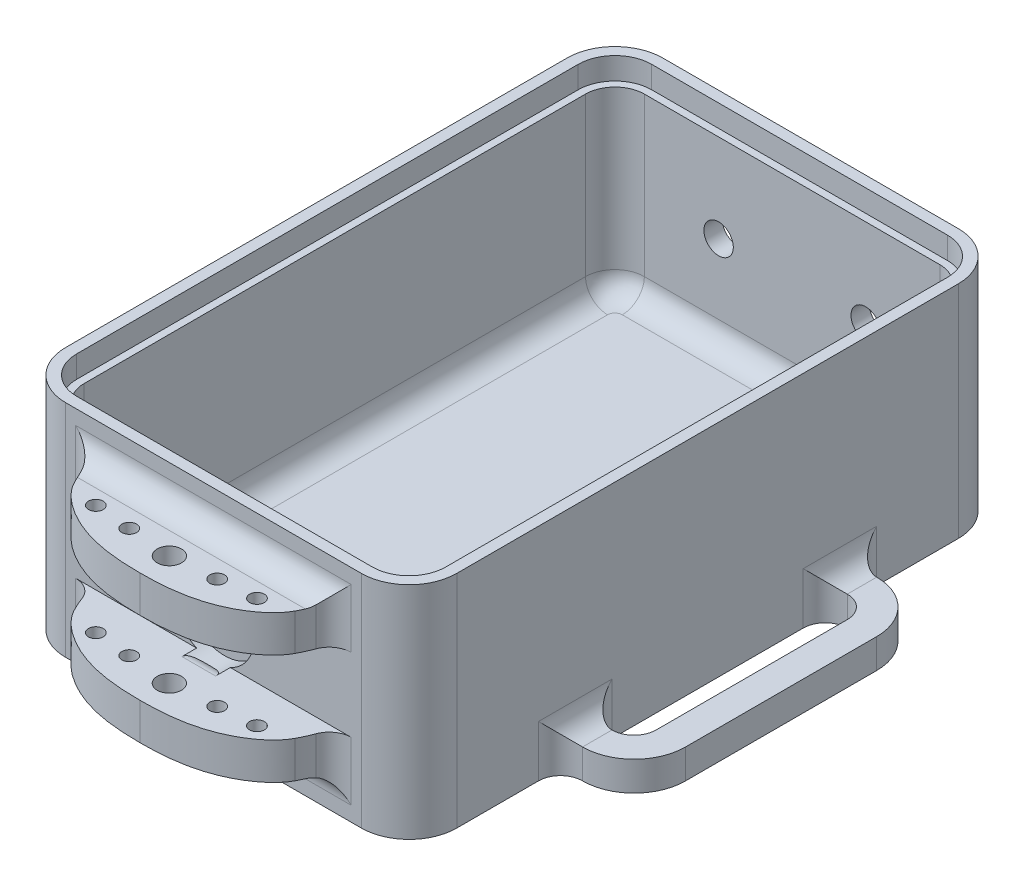
SolidWorks part; units mm, degrees
ref_plane "Front Plane" through (0, 0, 0) normal (0, 0, 1) x (1, 0, 0)
ref_plane "Top Plane" through (0, 0, 0) normal (0, 1, 0) x (1, 0, 0)
ref_plane "Right Plane" through (0, 0, 0) normal (1, 0, 0) x (0, 0, -1)
sketch "Sketch1" plane through (0, 0, 0) normal (0, 1, 0) x (1, 0, 0)
  line L0 (0, 36.2013) -> (0, -37.8247) construction
  line L1 (-30.7359, 0) -> (33.658, 0) construction
  line L3 (-20.1, -39.1) -> (20.1, -39.1)
  line L4 (-25.1, -34.1) -> (-25.1, 34.1)
  line L5 (-20.1, 39.1) -> (20.1, 39.1)
  line L6 (25.1, -34.1) -> (25.1, 34.1)
  line L7 (-25.1, -39.1) -> (25.1, 39.1) construction
  line L8 (-25.1, 39.1) -> (25.1, -39.1) construction
  line L9 (-20.1, -38.1) -> (20.1, -38.1)
  line L10 (-24.1, -34.1) -> (-24.1, 34.1)
  line L11 (-20.1, 38.1) -> (20.1, 38.1)
  line L12 (24.1, -34.1) -> (24.1, 34.1)
  line L13 (-24.1, -38.1) -> (24.1, 38.1) construction
  line L14 (-24.1, 38.1) -> (24.1, -38.1) construction
  line L15 (-20.1, -40.6) -> (20.1, -40.6)
  line L16 (-26.6, -34.1) -> (-26.6, 34.1)
  line L17 (-20.1, 40.6) -> (20.1, 40.6)
  line L18 (26.6, -34.1) -> (26.6, 34.1)
  line L19 (-26.6, -40.6) -> (26.6, 40.6) construction
  line L20 (-26.6, 40.6) -> (26.6, -40.6) construction
  arc A0 (25.1, -34.1) -> (20.1, -39.1) centre (20.1, -34.1) cw
  arc A1 (-20.1, -39.1) -> (-25.1, -34.1) centre (-20.1, -34.1) cw
  arc A2 (25.1, 34.1) -> (20.1, 39.1) centre (20.1, 34.1) ccw
  arc A3 (-20.1, 39.1) -> (-25.1, 34.1) centre (-20.1, 34.1) ccw
  arc A4 (-20.1, -38.1) -> (-24.1, -34.1) centre (-20.1, -34.1) cw
  arc A5 (24.1, -34.1) -> (20.1, -38.1) centre (20.1, -34.1) cw
  arc A6 (24.1, 34.1) -> (20.1, 38.1) centre (20.1, 34.1) ccw
  arc A7 (-20.1, 38.1) -> (-24.1, 34.1) centre (-20.1, 34.1) ccw
  arc A8 (-20.1, -40.6) -> (-26.6, -34.1) centre (-20.1, -34.1) cw
  arc A9 (26.6, -34.1) -> (20.1, -40.6) centre (20.1, -34.1) cw
  arc A10 (26.6, 34.1) -> (20.1, 40.6) centre (20.1, 34.1) ccw
  arc A11 (-20.1, 40.6) -> (-26.6, 34.1) centre (-20.1, 34.1) ccw
  point P5 (0, 0)
  point P22 (0, 0)
  point P40 (0, 0)
  dimension "D3" = 5
  dimension "D6" = 4
  dimension "D9" = 6.5
  dimension "D1" = 50.2
  dimension "D2" = 78.2
  dimension "D4" = 1
  dimension "D5" = 1
  dimension "D7" = 1.5
  dimension "D8" = 1.5
extrude "Boss-Extrude1" add sketch "Sketch1" along normal blind 30 contours L17 A11 L16 A8 L15 A9 L18 A10 A3 L5 A2 L6 A0 L3 A1 L4 region at (-24.0098, 0, 38.0098)
extrude "Boss-Extrude2" add sketch "Sketch1<3>" along normal blind 27 contours L5 A3 L4 A1 L3 A0 L6 A2 A7 L11 A6 L12 A5 L9 A4 L10 region at (-22.9784, 0, 36.9784)
sketch "Sketch1<3>" plane through (0, 0, 0) normal (0, 1, 0) x (1, 0, 0) same geometry as "Sketch1"
extrude "Boss-Extrude3" add sketch "Sketch1<4>" along normal blind 2.5 contours L11 A7 L10 A4 L9 A5 L12 A6 region at (0, 0, 0)
sketch "Sketch1<4>" plane through (0, 0, 0) normal (0, 1, 0) x (1, 0, 0) same geometry as "Sketch1"
fillet "Fillet1" radius 3 8 edges at (22.9284, 2.5, -36.9284) (24.1, 2.5, 0) (22.9284, 2.5, 36.9284) (0, 2.5, 38.1) (-22.9284, 2.5, 36.9284) (-24.1, 2.5, 0) (-22.9284, 2.5, -36.9284) (0, 2.5, -38.1)
sketch "Sketch3" plane through (0, 0, -40.6) normal (0, 0, -1) x (-1, 0, 0)
  line L0 (-31.6909, 15) -> (38.2468, 15) construction
  line L1 (0, 0) -> (0, 30) construction
  line L2 (20.1, 0) -> (-20.1, 0) construction
  line L3 (20.1, 30) -> (-20.1, 30) construction
  circle A0 centre (-10, 15) radius 2
  circle A1 centre (10, 15) radius 2
  point P8 (0, 15)
  dimension "D1" = 4
  dimension "D2" = 20
extrude "Bornier" cut sketch "Sketch3" against normal up to next
sketch "Sketch4" plane through (0, 0, 0) normal (0, -1, 0) x (1, 0, 0)
  line L0 (26.6, 34.1) -> (26.6, -34.1) construction
  line L1 (32.6, 16) -> (26.6, 16)
  line L2 (32.6, 16) -> (32.6, -16)
  line L3 (32.6, -16) -> (26.6, -16)
  line L4 (26.6, 16) -> (26.6, -16)
  line L5 (32.6, 16) -> (26.6, -16) construction
  line L6 (32.6, -16) -> (26.6, 16) construction
  line L7 (0, 0) -> (58.1127, 0) construction
  line L8 (26.6, -20) -> (36.6, -20)
  line L13 (-26.6, 20) -> (-26.6, 16)
  line L14 (-32.6, 16) -> (-26.6, 16)
  line L15 (36.6, -20) -> (36.6, 20)
  line L16 (36.6, 20) -> (26.6, 20)
  line L17 (26.6, 20) -> (26.6, 16)
  line L18 (26.6, -20) -> (26.6, -16)
  line L19 (0, 0) -> (0, -47.7172) construction
  line L20 (-36.6, -20) -> (-36.6, 20)
  line L21 (-36.6, 20) -> (-26.6, 20)
  line L22 (-26.6, -20) -> (-36.6, -20)
  line L23 (-26.6, -20) -> (-26.6, -16)
  line L24 (-32.6, -16) -> (-26.6, -16)
  line L25 (-32.6, 16) -> (-32.6, -16)
  point P0 (29.6, 0)
  line M13 (26.6, -34.1) -> (26.6, 34.1)
  line M17 (-26.6, 34.1) -> (-26.6, -34.1)
  dimension "D1" = 6
  dimension "D2" = 4
  dimension "D3" = 4
  dimension "D4" = 40
extrude "Boss-Extrude4" add sketch "Sketch4" against normal blind 4 contours L15 L16 L1 L2 L3 L8 M13 | L25 L14 L21 L20 L22 L24 M17 region at (33.4462, 0, 0) region at (-33.4462, 0, 0)
fillet "Fillet2" radius 3 16 edges at (32.6, 2, 16) (32.6, 2, -16) (26.6, 2, -20) (26.6, 2, -16) (26.6, 4, -18) (26.6, 4, 18) (26.6, 2, 20) (26.6, 2, 16) (-32.6, 2, -16) (-26.6, 2, -20) (-26.6, 4, -18) (-26.6, 2, -16) (-26.6, 4, 18) (-26.6, 2, 20) (-26.6, 2, 16) (-32.6, 2, 16)
fillet "Fillet3" radius 7 4 edges at (-36.6, 2, -20) (-36.6, 2, 20) (36.6, 2, -20) (36.6, 2, 20)
ref_plane "Plane1" through (0, 15, 0) normal (0, -1, 0) x (-1, 0, 0)
sketch "Sketch5" plane through (0, 15, 0) normal (0, -1, 0) x (-1, 0, 0)
  line L0 (0, 0) -> (0, -62.5379) construction
  line L1 (16.5227, -40.6) -> (-16.5227, -40.6)
  line L2 (20.1, -40.6) -> (-20.1, -40.6) construction
  line L3 (20.1, -38.1) -> (-20.1, -38.1) construction
  line L5 (0, -46.6) -> (-26.3183, -44.2974) construction
  arc A0 (-16.5227, -40.6) -> (-15.0258, -44.5515) centre (0, -36.6) ccw
  circle A1 centre (0, -46.6) radius 1.65
  circle A2 centre (-5.9772, -46.0771) radius 1
  circle A3 centre (-10.9581, -45.6413) radius 1
  circle A4 centre (10.9581, -45.6413) radius 1
  circle A5 centre (5.9772, -46.0771) radius 1
  arc A6 (15.0258, -44.5515) -> (16.5227, -40.6) centre (0, -36.6) ccw
  spline S0 degree 3 poles (-15.0258, -44.5515) (-14.2287, -46.0577) (-9.3456, -49.9684) (-3.8447, -50.6007) (0, -50.6007) knots 0 0 0 0 0.327379 1 1 1 1
  spline S1 degree 3 poles (15.0258, -44.5515) (14.2287, -46.0577) (9.3456, -49.9684) (3.8447, -50.6007) (0, -50.6007) knots 0 0 0 0 0.327379 1 1 1 1
  point P23 (0, 0)
  point P25 (-15.49, -43.6043)
  point P27 (-15.0252, -44.5526)
  point P28 (-10.9581, -48.2542)
  point P29 (0, 0)
  point P30 (-5.9772, -50.1054)
  point P31 (0, -50.5948)
  point P36 (0, 0)
  point P37 (0, 0)
  point P38 (0, 0)
  point P39 (0, 0)
  point P40 (0, 0)
  point P41 (0, 0)
  point P42 (0, 0)
  dimension "D2" = 17
  dimension "D3" = 3.3
  dimension "D6" = 2
  dimension "D7" = 2
  dimension "D1" = 1.5
  dimension "D4" = 10
  dimension "D5" = 85
  dimension "D8" = 6
  dimension "D9" = 5
extrude "Boss-Extrude6" add sketch "Sketch5" along normal blind 10 and the other way blind 10
sketch "Sketch6" plane through (0, 0, 0) normal (1, 0, 0) x (0, 0, -1)
  line L0 (-40.6, 30) -> (-40.6, 0) construction
  line L1 (-50.6007, 10) -> (-40.6, 10)
  line L2 (-50.6007, 10) -> (-50.6007, 20)
  line L3 (-50.6007, 20) -> (-40.6, 20)
  line L4 (-40.6, 10) -> (-40.6, 20)
  line L5 (-50.6007, 10) -> (-40.6, 20) construction
  line L6 (-50.6007, 20) -> (-40.6, 10) construction
  line L8 (-4.0719, 15) -> (-59.9731, 15) construction
  line L9 (-40.26, 15) -> (40.26, 15) construction
  line L11 (-50.6007, 25) -> (-50.6007, 5) construction
  point P0 (-45.6003, 15)
  dimension "D1" = 10
extrude "Cut-Extrude2" cut sketch "Sketch6" against normal through all both and the other way through all
fillet "Fillet4" radius 3 6 edges at (16.5227, 7.5, 40.6) (0, 5, 40.6) (16.5227, 22.5, 40.6) (0, 25, 40.6) (-16.5227, 7.5, 40.6) (-16.5227, 22.5, 40.6)
sketch "Sketch7" plane through (0, 0, 40.6) normal (0, 0, 1) x (1, 0, 0)
  line L0 (0, 0) -> (0, 30) construction
  line L1 (-20.1, 0) -> (20.1, 0) construction
  line L2 (18.6652, 15) -> (-18.6652, 15) construction
  line L3 (-40.26, 15) -> (40.26, 15) construction
  line L5 (-6.0208, 18) -> (-13, 18)
  line L6 (-13, 18) -> (-13, 12)
  line L7 (-13, 12) -> (-6.0208, 12)
  line L8 (-9, 18) -> (-9, 12)
  arc A0 (-3.8958, 11.1176) -> (-3.8958, 18.8824) centre (0, 15) ccw
  arc A1 (-6.0208, 12) -> (-3.8958, 11.1176) centre (-6.0208, 9) cw
  arc A2 (-6.0208, 18) -> (-3.8958, 18.8824) centre (-6.0208, 21) ccw
  point P8 (0, 15)
  point P9 (0, 15)
  line M10 (-18.735, 10) -> (18.735, 10)
  line M19 (18.735, 20) -> (-18.735, 20)
  dimension "D1" = 11
  dimension "D5" = 3
  dimension "D2" = 6
  dimension "D3" = 13
  dimension "D4" = 4
extrude "Cut-Extrude3" cut sketch "Sketch7" against normal blind 1.5 contours A2 L5 L8 L7 A1 A0 M10 M19 | A0 A2 L5 L6 L7 A1 region at (-1.4206, 15, 40.6)
extrude "Cut-Extrude4" cut sketch "Sketch7<3>" against normal up to next contours L8 L5 L6 L7 region at (-11, 15, 40.6)
sketch "Sketch7<3>" plane through (0, 0, 40.6) normal (0, 0, 1) x (1, 0, 0) same geometry as "Sketch7"
fillet "Fillet5" radius 2 2 edges at (0, 10, 40.6) (0, 20, 40.6)
